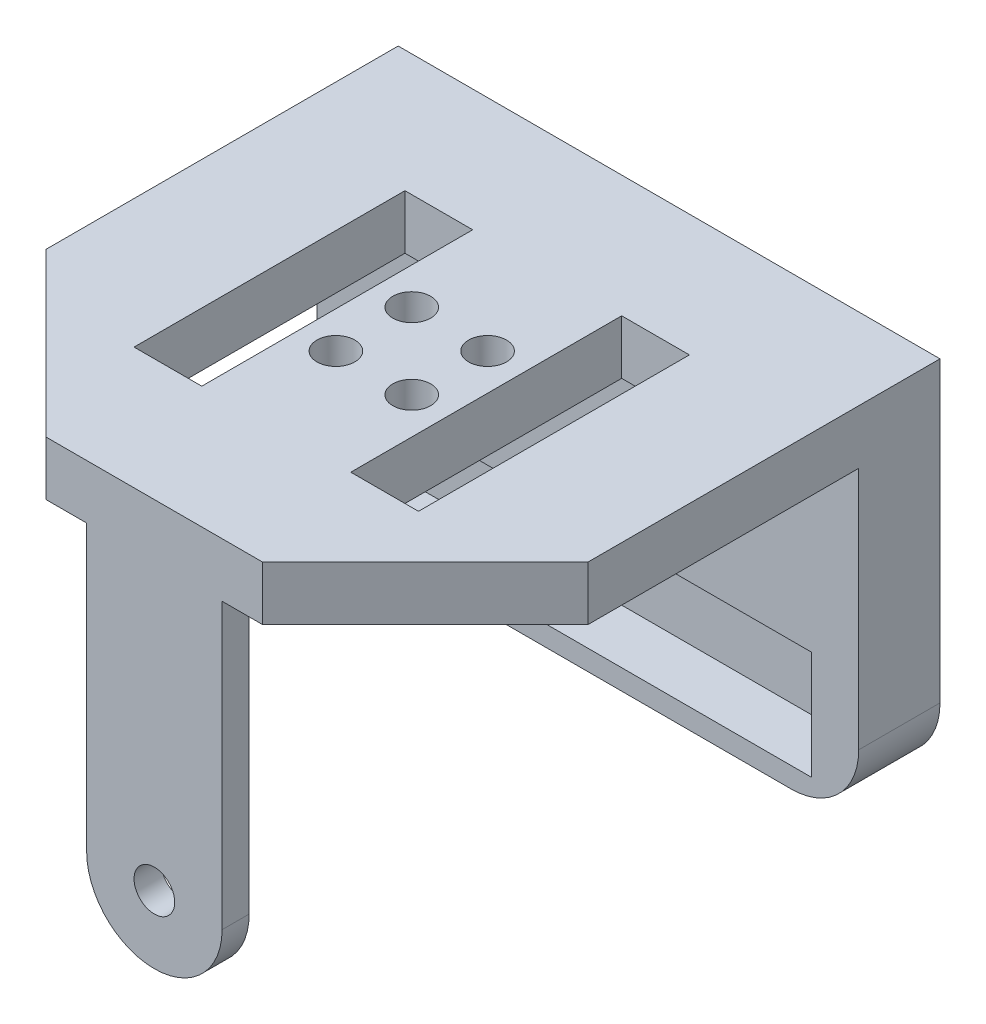
SolidWorks part; units mm, degrees
ref_plane "Front Plane" through (0, 0, 0) normal (0, 0, 1) x (1, 0, 0)
ref_plane "Top Plane" through (0, 0, 0) normal (0, 1, 0) x (1, 0, 0)
ref_plane "Right Plane" through (0, 0, 0) normal (1, 0, 0) x (0, 0, -1)
sketch "Schizzo3" plane through (0, 0, 0) normal (0, 0, 1) x (1, 0, 0)
  line L6 (-20, -13.5) -> (20, -13.5)
  line L13 (-20, -13.5) -> (-20, 13.5)
  line L14 (-20, 13.5) -> (20, 13.5)
  line L15 (20, -13.5) -> (20, 13.5)
  line L16 (-20, -13.5) -> (20, 13.5) construction
  line L17 (-20, 13.5) -> (20, -13.5) construction
  point P0 (0, 0)
  point P1 (0, 0)
  dimension "D1" = 40
  dimension "D2" = 27
extrude "Estrusione-Estrusione1" add sketch "Schizzo3" along normal blind 6
sketch "Schizzo4" plane through (0, 0, 6) normal (0, 0, 1) x (1, 0, 0)
  line L1 (-16.5, -4) -> (16.5, -4)
  line L2 (-16.5, -4) -> (-16.5, -12)
  line L3 (-16.5, -12) -> (16.5, -12)
  line L4 (16.5, -4) -> (16.5, -12)
  line L5 (-16.5, -4) -> (16.5, -12) construction
  line L6 (-16.5, -12) -> (16.5, -4) construction
  point P0 (0, -8)
  dimension "D1" = 33
  dimension "D2" = 8
  dimension "D3" = 8
extrude "Taglio-Estrusione1" cut sketch "Schizzo4" against normal blind 4
sketch "Schizzo5" plane through (0, 0, 2) normal (0, 0, 1) x (1, 0, 0)
  line L0 (-16.5, -4) -> (-16.5, -12) construction
  circle A0 centre (0, -8) radius 1.05
  point P6 (-16.5, -8)
  dimension "D1" = 2.1
extrude "Taglio-Estrusione2" cut sketch "Schizzo5" against normal through all
sketch "Schizzo6" plane through (0, 0, 6) normal (0, 0, 1) x (1, 0, 0)
  line L0 (20, -13.5) -> (20, 13.5) construction
  line L1 (-20, 13.5) -> (20, 13.5)
  line L2 (-20, 13.5) -> (-20, 9.5)
  line L3 (-20, 9.5) -> (20, 9.5)
  line L4 (20, 13.5) -> (20, 9.5)
  dimension "D1" = 4
extrude "Estrusione-Estrusione2" add sketch "Schizzo6" along normal blind 32 contours L2 L1 L4 L3
sketch "Schizzo7" plane through (0, 9.5, 0) normal (0, -1, 0) x (1, 0, 0)
  line L0 (-20, 38) -> (20, 38) construction
  line L1 (-5, 38) -> (5, 38)
  line L2 (-5, 38) -> (-5, 36)
  line L3 (-5, 36) -> (5, 36)
  line L4 (5, 38) -> (5, 36)
  point P6 (0, 38)
  point P7 (0, 36)
  dimension "D1" = 10
  dimension "D2" = 2
extrude "Estrusione-Estrusione3" add sketch "Schizzo7" along normal blind 26
sketch "Schizzo8" plane through (0, 13.5, 0) normal (0, 1, 0) x (1, 0, 0)
  line L0 (0, 0) -> (0, -38) construction
  line L1 (-20, -38) -> (20, -38) construction
  line L2 (-20, -19) -> (20, -19) construction
  line L3 (-20, -38) -> (-20, 0) construction
  line L4 (20, -38) -> (20, 0) construction
  line L5 (10.5, -9) -> (5.5, -9)
  line L6 (-10.5, -29) -> (-5.5, -29)
  line L7 (-10.5, -29) -> (-10.5, -9)
  line L8 (-10.5, -9) -> (-5.5, -9)
  line L9 (-5.5, -29) -> (-5.5, -9)
  line L10 (-10.5, -29) -> (-5.5, -9) construction
  line L11 (-10.5, -9) -> (-5.5, -29) construction
  line L12 (5.5, -29) -> (5.5, -9)
  line L13 (10.5, -29) -> (5.5, -29)
  line L14 (10.5, -29) -> (10.5, -9)
  line L15 (-20, -26) -> (-8, -38)
  line L16 (-8, -38) -> (-20, -38)
  line L17 (-20, -38) -> (-20, -26)
  line L18 (8, -38) -> (20, -38)
  line L19 (20, -26) -> (8, -38)
  line L20 (20, -38) -> (20, -26)
  circle A0 centre (-2.8, -16.2) radius 1.4
  circle A1 centre (-2.8, -21.8) radius 1.4
  circle A2 centre (2.8, -21.8) radius 1.4
  circle A3 centre (2.8, -16.2) radius 1.4
  point P19 (-8, -19)
  dimension "D1" = 2.8
  dimension "D2" = 2.8
  dimension "D3" = 2.8
  dimension "D4" = 5
  dimension "D5" = 20
  dimension "D6" = 8
  dimension "D7" = 12
  dimension "D8" = 12
extrude "Taglio-Estrusione3" cut sketch "Schizzo8" against normal through all
fillet "Raccordo1" radius 5 4 edges at (-5, -16.5, 37) (5, -16.5, 37) (20, -13.5, 3) (-20, -13.5, 3)
sketch "Schizzo9" plane through (0, 0, 36) normal (0, 0, -1) x (-1, 0, 0)
  line L2 (-5, -11.5) -> (5, -11.5) construction
  line L3 (-5, -11.5) -> (-5, 9.5) construction
  line L4 (5, -11.5) -> (5, 9.5) construction
  circle A0 centre (0, -11.5) radius 1.5
  point P8 (0, -11.5)
  dimension "D1" = 3
extrude "Taglio-Estrusione4" cut sketch "Schizzo9" against normal up to next
